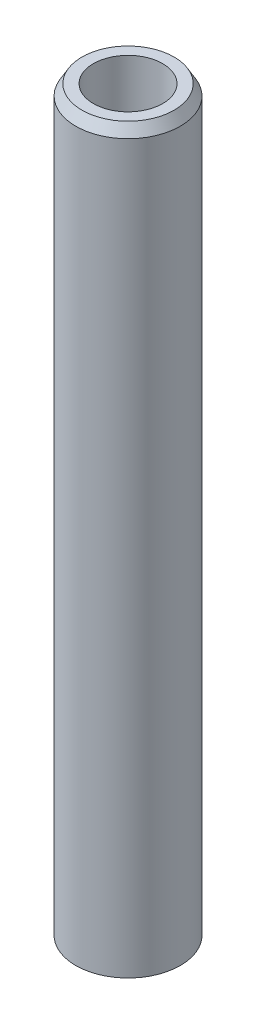
SolidWorks part; units mm, degrees
ref_plane "Front Plane" through (0, 0, 0) normal (0, 0, 1) x (1, 0, 0)
ref_plane "Top Plane" through (0, 0, 0) normal (0, 1, 0) x (1, 0, 0)
ref_plane "Right Plane" through (0, 0, 0) normal (1, 0, 0) x (0, 0, -1)
sketch "Sketch1" plane through (0, 0, 0) normal (0, 1, 0) x (1, 0, 0)
  circle A0 centre (0, 0) radius 27.5
  dimension "SHAFT_OD" = 55
extrude "Boss-Extrude1" add sketch "Sketch1" along normal blind 391.033
sketch "Sketch2" plane through (0, 0, 0) normal (0, 1, 0) x (1, 0, 0)
  circle A0 centre (0, 0) radius 18.2114
  dimension "BORE_D" = 36.4229
extrude "Cut-Extrude1" cut sketch "Sketch2" along normal through all
chamfer "Chamfer1" distance 5.6557 angle 30 2 edges at (0, 391.033, 27.5) (0, 0, 27.5) first distance on face at (0, 391.033, 27.5) first distance on face at (0, 0, 18.2114)
